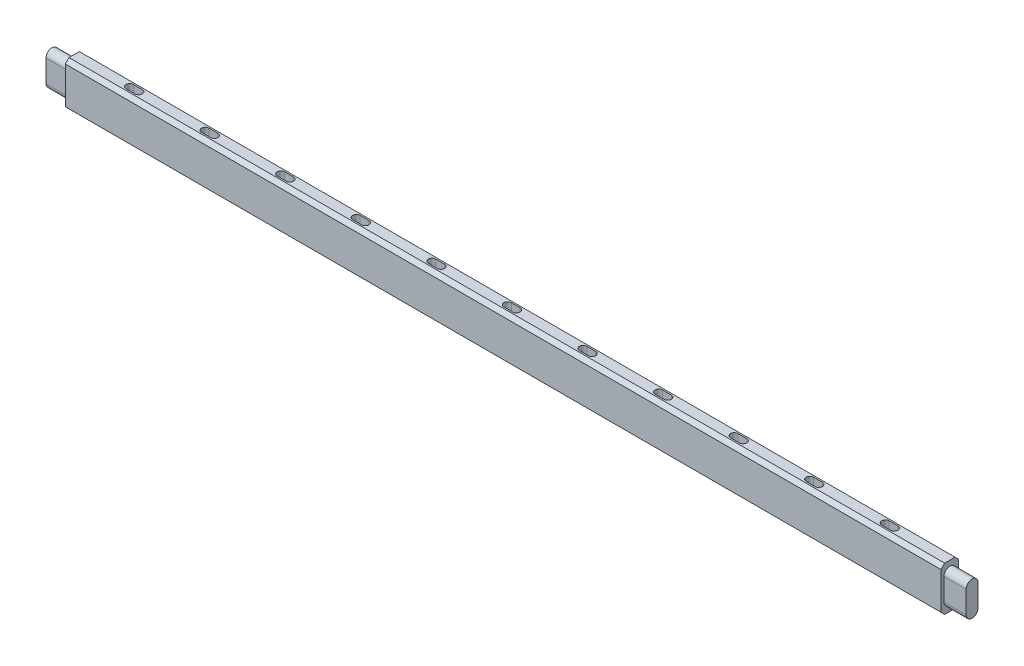
SolidWorks part; units mm, degrees
ref_plane "Front" through (0, 0, 0) normal (0, 0, 1) x (1, 0, 0)
ref_plane "Top" through (0, 0, 0) normal (0, 1, 0) x (1, 0, 0)
ref_plane "Right" through (0, 0, 0) normal (1, 0, 0) x (0, 0, -1)
sketch "Esquisse1" plane through (0, 0, 0) normal (0, 0, 1) x (1, 0, 0)
  line L1 (0, 0) -> (1182, 0)
  line L2 (0, 0) -> (0, 60)
  line L3 (0, 60) -> (1182, 60)
  line L4 (1182, 0) -> (1182, 60)
  dimension "D1" = 1182
  dimension "D2" = 60
extrude "Boss.-Extru.1" add sketch "Esquisse1" along normal blind 24
sketch "Esquisse2" plane through (0, 0, 0) normal (-1, 0, 0) x (0, 0, 1)
  line L0 (12, 0) -> (12, 60) construction
  line L1 (24, 0) -> (0, 0) construction
  line L2 (24, 60) -> (0, 60) construction
  line L3 (12, 15) -> (12, 45) construction
  line L4 (4, 15) -> (4, 45)
  line L5 (20, 15) -> (20, 45)
  arc A0 (4, 15) -> (20, 15) centre (12, 15) ccw
  arc A1 (20, 45) -> (4, 45) centre (12, 45) ccw
  point P8 (12, 30)
  dimension "D1" = 16
  dimension "D2" = 30
extrude "Boss.-Extru.2" add sketch "Esquisse2" along normal blind 30
extrude "Boss.-Extru.3" add sketch "Esquisse2<2>" against normal blind 30 from vertex starting at point (1182, 60, 0)
sketch "Esquisse2<2>" plane through (0, 0, 0) normal (-1, 0, 0) x (0, 0, 1) same geometry as "Esquisse2"
chamfer "Chanfrein1" distance 5 angle 45 4 edges at (591, 0, 24) (591, 0, 0) (591, 60, 0) (591, 60, 24)
sketch "Esquisse3" plane through (0, 60, 0) normal (0, 1, 0) x (1, 0, 0)
  line L0 (591, -19) -> (591, -5) construction
  line L1 (0, -19) -> (1182, -19) construction
  line L2 (591, -12) -> (693, -12) construction
  line L3 (642, -12) -> (642, -5) construction
  line L4 (1182, -5) -> (0, -5) construction
  line L5 (387, -12) -> (489, -12) construction
  line L7 (591, -12) -> (489, -12) construction
  line L8 (483, -12) -> (495, -12) construction
  line L9 (483, -7) -> (495, -7)
  line L10 (483, -17) -> (495, -17)
  line L11 (381, -12) -> (393, -12) construction
  line L12 (381, -7) -> (393, -7)
  line L13 (381, -17) -> (393, -17)
  line L14 (279, -12) -> (291, -12) construction
  line L15 (279, -7) -> (291, -7)
  line L16 (279, -17) -> (291, -17)
  line L17 (177, -12) -> (189, -12) construction
  line L18 (177, -7) -> (189, -7)
  line L19 (177, -17) -> (189, -17)
  line L20 (75, -12) -> (87, -12) construction
  line L21 (75, -7) -> (87, -7)
  line L22 (75, -17) -> (87, -17)
  line L23 (591, -16) -> (597, -12) construction
  line L24 (591, -16) -> (597, -12) construction
  line L25 (585, -12) -> (597, -12) construction
  line L26 (585, -7) -> (597, -7)
  line L27 (585, -17) -> (597, -17)
  line L29 (1107, -12) -> (1095, -12) construction
  line L30 (1107, -7) -> (1095, -7)
  line L31 (1107, -17) -> (1095, -17)
  line L32 (1005, -12) -> (993, -12) construction
  line L33 (1005, -7) -> (993, -7)
  line L34 (1005, -17) -> (993, -17)
  line L35 (903, -12) -> (891, -12) construction
  line L36 (903, -7) -> (891, -7)
  line L37 (903, -17) -> (891, -17)
  line L38 (801, -12) -> (789, -12) construction
  line L39 (801, -7) -> (789, -7)
  line L40 (801, -17) -> (789, -17)
  line L41 (699, -12) -> (687, -12) construction
  line L42 (699, -7) -> (687, -7)
  line L43 (699, -17) -> (687, -17)
  line L125 (-27, -12) -> (-15, -12) construction
  line L126 (-27, -7) -> (-15, -7)
  line L127 (-27, -17) -> (-15, -17)
  line L128 (-27, -12) -> (-15, -12) construction
  line L129 (-27, -7) -> (-15, -7)
  line L130 (-27, -17) -> (-15, -17)
  arc A0 (483, -7) -> (483, -17) centre (483, -12) ccw
  arc A1 (495, -17) -> (495, -7) centre (495, -12) ccw
  arc A2 (381, -7) -> (381, -17) centre (381, -12) ccw
  arc A3 (393, -17) -> (393, -7) centre (393, -12) ccw
  arc A4 (279, -7) -> (279, -17) centre (279, -12) ccw
  arc A5 (291, -17) -> (291, -7) centre (291, -12) ccw
  arc A6 (177, -7) -> (177, -17) centre (177, -12) ccw
  arc A7 (189, -17) -> (189, -7) centre (189, -12) ccw
  arc A8 (75, -7) -> (75, -17) centre (75, -12) ccw
  arc A9 (87, -17) -> (87, -7) centre (87, -12) ccw
  arc A10 (585, -7) -> (585, -17) centre (585, -12) ccw
  arc A11 (597, -17) -> (597, -7) centre (597, -12) ccw
  arc A14 (1107, -7) -> (1107, -17) centre (1107, -12) cw
  arc A15 (1095, -17) -> (1095, -7) centre (1095, -12) cw
  arc A16 (1005, -7) -> (1005, -17) centre (1005, -12) cw
  arc A17 (993, -17) -> (993, -7) centre (993, -12) cw
  arc A18 (903, -7) -> (903, -17) centre (903, -12) cw
  arc A19 (891, -17) -> (891, -7) centre (891, -12) cw
  arc A20 (801, -7) -> (801, -17) centre (801, -12) cw
  arc A21 (789, -17) -> (789, -7) centre (789, -12) cw
  arc A22 (699, -7) -> (699, -17) centre (699, -12) cw
  arc A23 (687, -17) -> (687, -7) centre (687, -12) cw
  arc A80 (-27, -7) -> (-27, -17) centre (-27, -12) ccw
  arc A81 (-15, -17) -> (-15, -7) centre (-15, -12) ccw
  point P10 (489, -12)
  point P19 (387, -12)
  point P26 (285, -12)
  point P33 (183, -12)
  point P40 (81, -12)
  point P49 (591, -12)
  point P59 (1101, -12)
  point P66 (999, -12)
  point P73 (897, -12)
  point P80 (795, -12)
  point P87 (693, -12)
  point P94 (-11, -16)
  point P104 (-11, -16)
  point P111 (-11, -16)
  point P118 (-11, -16)
  point P125 (-16, -16)
  point P132 (-16, -16)
  point P139 (-16, -16)
  point P146 (-16, -16)
  point P153 (-55, -16)
  point P160 (-55, -16)
  point P167 (-55, -16)
  point P174 (-55, -16)
  point P181 (-55, -16)
  point P188 (-55, -16)
  point P195 (-55, -16)
  point P202 (-55, -16)
  point P209 (-320, -16)
  point P216 (-320, -16)
  point P223 (-19, -12)
  point P230 (-19, -12)
  point P237 (-34, -12)
  point P244 (-34, -12)
  point P251 (-22, -12)
  point P258 (-22, -12)
  point P265 (-21, -12)
  point P272 (-21, -12)
  point P279 (-21, -12)
  point P286 (-21, -12)
  point P293 (-21, -12)
  dimension "D1" = 10
  dimension "D2" = 204
  dimension "D3" = 12
  dimension "D4" = 6
  dimension "D5" = 102
extrude "Enlèv. mat.-Extru.1" cut sketch "Esquisse3" against normal blind 15
sketch "Esquisse5" [suppressed] plane through (0, 60, 0) normal (0, 1, 0) x (1, 0, 0)
  line L0 (285, -24) -> (285, 0) construction
  line L1 (570, -24) -> (0, -24) construction
  line L2 (285, -12) -> (387, -12) construction
  line L3 (336, -12) -> (336, -5) construction
  line L4 (570, -5) -> (0, -5) construction
  line L5 (0, 0) -> (570, 0) construction
  line L6 (285, -5) -> (285, 0) construction
  line L7 (285, -12) -> (183, -12) construction
  line L8 (177, -12) -> (189, -12) construction
  line L9 (177, -7) -> (189, -7)
  line L10 (177, -17) -> (189, -17)
  line L11 (75, -12) -> (87, -12) construction
  line L12 (75, -7) -> (87, -7)
  line L13 (75, -17) -> (87, -17)
  line L23 (364.5901, -45.0509) -> (291, -12) construction
  line L24 (364.5901, -45.0509) -> (291, -12) construction
  line L25 (279, -12) -> (291, -12) construction
  line L26 (279, -7) -> (291, -7)
  line L27 (279, -17) -> (291, -17)
  line L38 (495, -12) -> (483, -12) construction
  line L39 (495, -7) -> (483, -7)
  line L40 (495, -17) -> (483, -17)
  line L41 (393, -12) -> (381, -12) construction
  line L42 (393, -7) -> (381, -7)
  line L43 (393, -17) -> (381, -17)
  line L557 (-27, -12) -> (-15, -12) construction
  line L558 (-27, -7) -> (-15, -7)
  line L559 (-27, -17) -> (-15, -17)
  line L560 (-129, -12) -> (-117, -12) construction
  line L561 (-129, -7) -> (-117, -7)
  line L562 (-129, -17) -> (-117, -17)
  line L563 (-231, -12) -> (-219, -12) construction
  line L564 (-231, -7) -> (-219, -7)
  line L565 (-231, -17) -> (-219, -17)
  line L566 (-333, -12) -> (-321, -12) construction
  line L567 (-333, -7) -> (-321, -7)
  line L568 (-333, -17) -> (-321, -17)
  line L569 (-27, -12) -> (-15, -12) construction
  line L570 (-27, -7) -> (-15, -7)
  line L571 (-27, -17) -> (-15, -17)
  line L572 (-129, -12) -> (-117, -12) construction
  line L573 (-129, -7) -> (-117, -7)
  line L574 (-129, -17) -> (-117, -17)
  line L575 (-231, -12) -> (-219, -12) construction
  line L576 (-231, -7) -> (-219, -7)
  line L577 (-231, -17) -> (-219, -17)
  line L578 (-333, -12) -> (-321, -12) construction
  line L579 (-333, -7) -> (-321, -7)
  line L580 (-333, -17) -> (-321, -17)
  arc A0 (177, -7) -> (177, -17) centre (177, -12) ccw
  arc A1 (189, -17) -> (189, -7) centre (189, -12) ccw
  arc A2 (75, -7) -> (75, -17) centre (75, -12) ccw
  arc A3 (87, -17) -> (87, -7) centre (87, -12) ccw
  arc A10 (279, -7) -> (279, -17) centre (279, -12) ccw
  arc A11 (291, -17) -> (291, -7) centre (291, -12) ccw
  arc A20 (495, -7) -> (495, -17) centre (495, -12) cw
  arc A21 (483, -17) -> (483, -7) centre (483, -12) cw
  arc A22 (393, -7) -> (393, -17) centre (393, -12) cw
  arc A23 (381, -17) -> (381, -7) centre (381, -12) cw
  arc A374 (-27, -7) -> (-27, -17) centre (-27, -12) ccw
  arc A375 (-15, -17) -> (-15, -7) centre (-15, -12) ccw
  arc A376 (-129, -7) -> (-129, -17) centre (-129, -12) ccw
  arc A377 (-117, -17) -> (-117, -7) centre (-117, -12) ccw
  arc A378 (-231, -7) -> (-231, -17) centre (-231, -12) ccw
  arc A379 (-219, -17) -> (-219, -7) centre (-219, -12) ccw
  arc A380 (-333, -7) -> (-333, -17) centre (-333, -12) ccw
  arc A381 (-321, -17) -> (-321, -7) centre (-321, -12) ccw
  point P10 (183, -12)
  point P19 (81, -12)
  point P26 (-169, -16.4919)
  point P33 (-272, -16.4919)
  point P49 (285, -12)
  point P55 (-66, -16.4919)
  point P80 (489, -12)
  point P87 (387, -12)
  point P94 (-225.2423, -16.4919)
  point P104 (-225.2423, -16.4919)
  point P111 (-225.2423, -16.4919)
  point P118 (-225.2423, -16.4919)
  point P125 (-230.2423, -16.4919)
  point P132 (-230.2423, -16.4919)
  point P139 (-230.2423, -16.4919)
  point P146 (-230.2423, -16.4919)
  point P153 (-269.2423, -16.4919)
  point P160 (-269.2423, -16.4919)
  point P167 (-269.2423, -16.4919)
  point P174 (-269.2423, -16.4919)
  point P181 (-269.2423, -16.4919)
  point P188 (-269.2423, -16.4919)
  point P195 (-269.2423, -16.4919)
  point P202 (-269.2423, -16.4919)
  point P209 (-534.2423, -16.4919)
  point P216 (-534.2423, -16.4919)
  point P223 (-375, -16.4919)
  point P230 (-66, -16.4919)
  point P237 (-169, -16.4919)
  point P244 (-272, -16.4919)
  point P251 (-375, -16.4919)
  point P258 (-66, -16.4919)
  point P265 (-169, -16.4919)
  point P272 (-272, -16.4919)
  point P279 (-375, -16.4919)
  point P286 (-66, -16.4919)
  point P293 (-169, -16.4919)
  point P300 (-272, -16.4919)
  point P307 (-375, -16.4919)
  point P314 (-66, -16.4919)
  point P321 (-169, -16.4919)
  point P328 (-272, -16.4919)
  point P335 (-375, -16.4919)
  point P342 (-66, -16.4919)
  point P349 (-169, -16.4919)
  point P356 (-272, -16.4919)
  point P363 (-375, -16.4919)
  point P370 (-66, -16.4919)
  point P377 (-169, -16.4919)
  point P384 (-272, -16.4919)
  point P391 (-375, -16.4919)
  point P398 (-66, -16.4919)
  point P405 (-169, -16.4919)
  point P412 (-272, -16.4919)
  point P419 (-375, -16.4919)
  point P426 (-66, -16.4919)
  point P433 (-169, -16.4919)
  point P440 (-272, -16.4919)
  point P447 (-375, -16.4919)
  point P454 (-66, -16.4919)
  point P461 (-169, -16.4919)
  point P468 (-272, -16.4919)
  point P475 (-375, -16.4919)
  point P482 (-55.5, -16.4919)
  point P489 (-158.5, -16.4919)
  point P496 (-261.5, -16.4919)
  point P503 (-364.5, -16.4919)
  point P510 (-55.5, -16.4919)
  point P517 (-158.5, -16.4919)
  point P524 (-261.5, -16.4919)
  point P531 (-364.5, -16.4919)
  point P538 (-57, -16.4919)
  point P545 (-160, -16.4919)
  point P552 (-263, -16.4919)
  point P559 (-366, -16.4919)
  point P566 (-57, -16.4919)
  point P573 (-160, -16.4919)
  point P580 (-263, -16.4919)
  point P587 (-366, -16.4919)
  point P594 (-59, -16.4919)
  point P601 (-163, -16.4919)
  point P608 (-267, -16.4919)
  point P615 (-371, -16.4919)
  point P622 (-59, -16.4919)
  point P629 (-163, -16.4919)
  point P636 (-267, -16.4919)
  point P643 (-371, -16.4919)
  point P650 (-59, -16.4919)
  point P657 (-163, -16.4919)
  point P664 (-267, -16.4919)
  point P671 (-371, -16.4919)
  point P678 (-59, -16.4919)
  point P685 (-163, -16.4919)
  point P692 (-267, -16.4919)
  point P699 (-371, -16.4919)
  point P706 (-59, -12)
  point P713 (-163, -12)
  point P720 (-267, -12)
  point P727 (-371, -12)
  point P734 (-59, -12)
  point P741 (-163, -12)
  point P748 (-267, -12)
  point P755 (-371, -12)
  point P762 (-59, -12)
  point P769 (-163, -12)
  point P776 (-267, -12)
  point P783 (-371, -12)
  point P790 (-59, -12)
  point P797 (-163, -12)
  point P804 (-267, -12)
  point P811 (-371, -12)
  point P818 (-7, -12)
  point P825 (-111, -12)
  point P832 (-215, -12)
  point P839 (-319, -12)
  point P846 (-7, -12)
  point P853 (-111, -12)
  point P860 (-215, -12)
  point P867 (-319, -12)
  point P874 (-7, -12)
  point P881 (-111, -12)
  point P888 (-215, -12)
  point P895 (-319, -12)
  point P902 (-7, -12)
  point P909 (-111, -12)
  point P916 (-215, -12)
  point P923 (-319, -12)
  point P930 (-22, -12)
  point P937 (-126, -12)
  point P944 (-230, -12)
  point P951 (-334, -12)
  point P958 (-22, -12)
  point P965 (-126, -12)
  point P972 (-230, -12)
  point P979 (-334, -12)
  point P986 (-20, -12)
  point P993 (-124, -12)
  point P1000 (-228, -12)
  point P1007 (-332, -12)
  point P1014 (-20, -12)
  point P1021 (-124, -12)
  point P1028 (-228, -12)
  point P1035 (-332, -12)
  point P1042 (-18, -12)
  point P1049 (-120, -12)
  point P1056 (-222, -12)
  point P1063 (-324, -12)
  point P1070 (-18, -12)
  point P1077 (-120, -12)
  point P1084 (-222, -12)
  point P1091 (-324, -12)
  point P1098 (-16, -12)
  point P1105 (-118, -12)
  point P1112 (-220, -12)
  point P1119 (-322, -12)
  point P1126 (-16, -12)
  point P1133 (-118, -12)
  point P1140 (-220, -12)
  point P1147 (-322, -12)
  point P1154 (-21, -12)
  point P1161 (-123, -12)
  point P1168 (-225, -12)
  point P1175 (-327, -12)
  point P1182 (-21, -12)
  point P1189 (-123, -12)
  point P1196 (-225, -12)
  point P1203 (-327, -12)
  point P1210 (-21, -12)
  point P1217 (-123, -12)
  point P1224 (-225, -12)
  point P1231 (-327, -12)
  point P1238 (-21, -12)
  point P1245 (-123, -12)
  point P1252 (-225, -12)
  point P1259 (-327, -12)
  point P1266 (-21, -12)
  point P1273 (-123, -12)
  point P1280 (-225, -12)
  point P1287 (-327, -12)
  point P1294 (-21, -12)
  point P1301 (-123, -12)
  point P1308 (-225, -12)
  point P1315 (-327, -12)
  point P1322 (-21, -12)
  point P1329 (-123, -12)
  point P1336 (-225, -12)
  point P1343 (-327, -12)
  dimension "D1" = 12
  dimension "D2" = 12
  dimension "D3" = 10
  dimension "D4" = 6
  dimension "D5" = 102
  dimension "D6" = 102
extrude "Enlèv. mat.-Extru.2" [suppressed] cut sketch "Esquisse5" against normal blind 15
